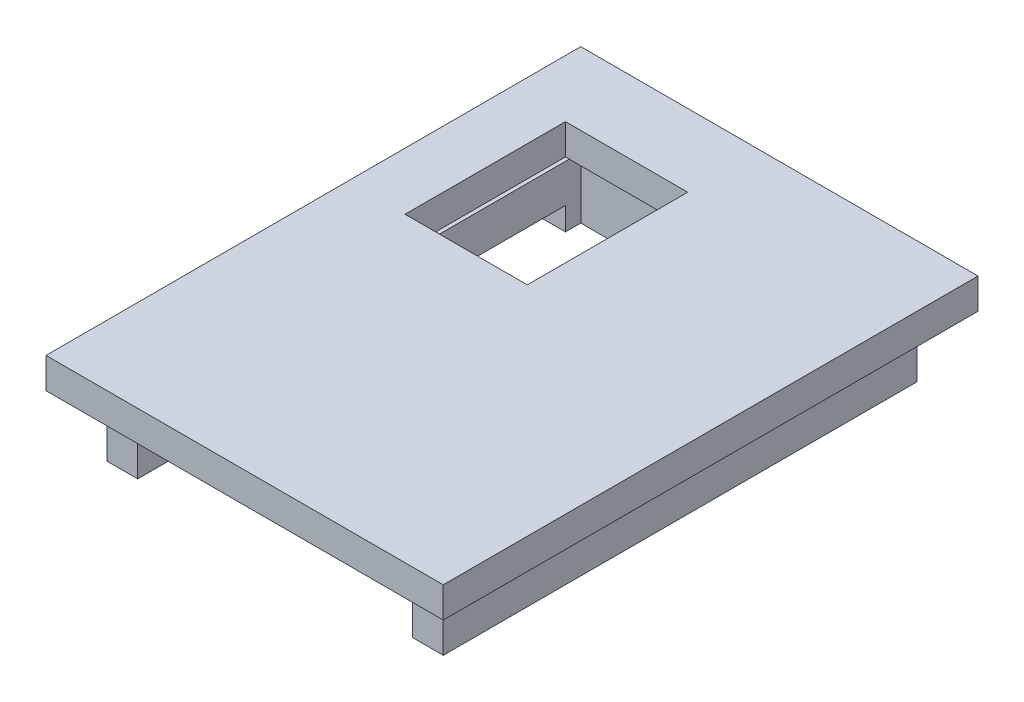
SolidWorks part; units mm, degrees
ref_plane "Płaszczyzna przednia" through (0, 0, 0) normal (0, 0, 1) x (1, 0, 0)
ref_plane "Płaszczyzna górna" through (0, 0, 0) normal (0, 1, 0) x (1, 0, 0)
ref_plane "Płaszczyzna prawa" through (0, 0, 0) normal (1, 0, 0) x (0, 0, -1)
sketch "Szkic1" plane through (0, 0, 0) normal (0, 1, 0) x (1, 0, 0)
  line L1 (-13, -17.5) -> (13, -17.5)
  line L2 (-13, -17.5) -> (-13, 17.5)
  line L3 (-13, 17.5) -> (13, 17.5)
  line L4 (13, -17.5) -> (13, 17.5)
  line L5 (-13, -17.5) -> (13, 17.5) construction
  line L6 (-13, 17.5) -> (13, -17.5) construction
  point P0 (0, 0)
  dimension "D1" = 26
  dimension "D2" = 35
extrude "Dodanie-wyciągnięcie1" add sketch "Szkic1" along normal blind 2
sketch "Szkic2" plane through (0, 0, 0) normal (0, -1, 0) x (1, 0, 0)
  line L5 (-9, 13.5) -> (9, 13.5)
  line L6 (-11, -15.5) -> (11, -15.5)
  line L10 (-11, -15.5) -> (-11, 15.5)
  line L11 (-11, 15.5) -> (11, 15.5)
  line L12 (11, -15.5) -> (11, 15.5)
  line L13 (-11, -15.5) -> (11, 15.5) construction
  line L14 (-11, 15.5) -> (11, -15.5) construction
  line L15 (9, 13.5) -> (9, -13.5)
  line L16 (9, -13.5) -> (-9, -13.5)
  line L17 (-9, -13.5) -> (-9, 13.5)
  line L18 (-13, 17.5) -> (13, 17.5) construction
  line L20 (13, 17.5) -> (13, -17.5) construction
  point P0 (0, 0)
  dimension "D2" = 2
  dimension "D3" = 2
  dimension "D4" = 2
  dimension "D5" = 2
  dimension "D6" = 2
  dimension "D7" = 2
extrude "Dodanie-wyciągnięcie2" add sketch "Szkic2" along normal blind 4
sketch "Szkic3" plane through (0, 0, 0) normal (0, -1, 0) x (1, 0, 0)
  line L0 (-9, -13.5) -> (-5.25, -13.5) construction
  line L1 (-5.25, -13.5) -> (-5.25, -7.5) construction
  line L2 (-9, -13.5) -> (9, -13.5) construction
  line L3 (-1.25, -12.75) -> (-9.25, -12.75)
  line L4 (-1.25, -12.75) -> (-1.25, -2.25)
  line L5 (-1.25, -2.25) -> (-9.25, -2.25)
  line L6 (-9.25, -12.75) -> (-9.25, -2.25)
  line L7 (-1.25, -12.75) -> (-9.25, -2.25) construction
  line L8 (-1.25, -2.25) -> (-9.25, -12.75) construction
  line L9 (-9, 13.5) -> (-9, -13.5) construction
  point P7 (-9, -13.5)
  dimension "D1" = 3.75
  dimension "D2" = 6
  dimension "D3" = 10.5
  dimension "D4" = 8
extrude "Wytnij-wyciągnięcie1" cut sketch "Szkic3" against normal through all
sketch "Szkic4" plane through (0, 0, 15.5) normal (0, 0, 1) x (1, 0, 0)
  line L0 (0, 0) -> (0, -1) construction
  line L1 (-13, 0) -> (13, 0) construction
  line L2 (-9, -1) -> (9, -1)
  line L3 (9, -1) -> (9, -4)
  line L4 (11, -4) -> (-11, -4) construction
  line L5 (9, -4) -> (-9, -4)
  line L6 (-9, -4) -> (-9, -1)
  point P7 (0, -1)
  dimension "D1" = 3
  dimension "D2" = 18
extrude "Wytnij-wyciągnięcie2" cut sketch "Szkic4" against normal up to surface (2 mm away) up to face at (0, -2, 13.5)
sketch "Szkic5" plane through (-11, 0, 0) normal (-1, 0, 0) x (0, 0, 1)
  line L0 (-15.5, -4) -> (-12.5, -4) construction
  line L1 (-15.5, -4) -> (-15.5, 0) construction
  line L2 (15.5, -4) -> (-15.5, -4) construction
  line L3 (-12.5, -4) -> (-12.5, -2.5)
  line L4 (-12.5, -2.5) -> (-3, -2.5)
  line L5 (-3, -2.5) -> (-3, -4)
  line L6 (-3, -4) -> (-12.5, -4)
  point P9 (-15.5, -4)
  dimension "D1" = 3
  dimension "D2" = 9.5
  dimension "D3" = 1.5
extrude "Wytnij-wyciągnięcie3" cut sketch "Szkic5" against normal up to surface (2 mm away) up to face at (-9, -1.25, 2)
